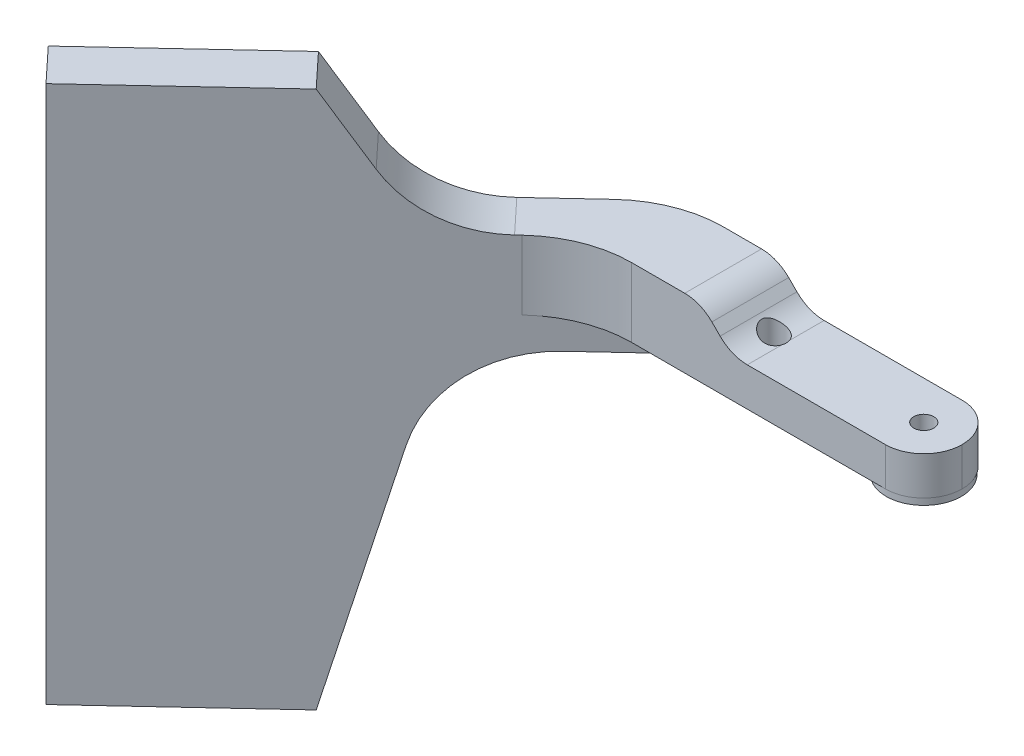
SolidWorks part; units mm, degrees
ref_plane "Front" through (0, 0, 0) normal (0, 0, 1) x (1, 0, 0)
ref_plane "Top" through (0, 0, 0) normal (0, 1, 0) x (1, 0, 0)
ref_plane "Right" through (0, 0, 0) normal (1, 0, 0) x (0, 0, -1)
sketch "Sketch1" plane through (0, 0, 0) normal (0, 1, 0) x (1, 0, 0)
  line L0 (0, 10) -> (0, 0)
  line L1 (0, 0) -> (42, 0)
  line L3 (0, 10) -> (42, 10)
  line L4 (42, 0) -> (42, 10)
  line L9 (0, 10) -> (-42.4185, -29.5559)
  line L10 (-42.4185, -29.5559) -> (-38.3265, -33.944)
  line L11 (0, 10) -> (4.092, 5.6119)
  line L12 (-38.3265, -33.944) -> (4.092, 5.6119)
  line L13 (0, 0) -> (-1.926, 0)
  line L14 (-1.926, 0) -> (0, 1.796)
  line L15 (0, 1.796) -> (0, 0)
  dimension "D1" = 10
  dimension "D2" = 42
  dimension "D3" = 223
  dimension "D4" = 58
  dimension "D5" = 6
  dimension "D6" = 270
extrude "Boss-Extrude1" add sketch "Sketch1" along normal blind 5 contours L10 L12 L1 L0 L9 | L1 L12 L11 L0 | L12 L1 L4 L3 L11 | L13 L0 L12
fillet "Fillet1" radius 5 2 edges at (42, 2.5, 0) (42, 2.5, -10)
sketch "Sketch2" plane through (0, 5, 0) normal (0, 1, 0) x (1, 0, 0)
  circle A0 centre (37, 5) radius 1.3
extrude "Cut-Extrude1" cut sketch "Sketch2" against normal blind 10
sketch "Sketch3" plane through (0, 5, 0) normal (0, 1, 0) x (1, 0, 0)
  line L0 (-42.4185, -29.5559) -> (-38.3265, -33.944)
  line L1 (-38.3265, -33.944) -> (-20.1263, -16.972)
  line L2 (-38.3265, -33.944) -> (-1.926, 0) construction
  line L3 (-20.1263, -16.972) -> (-24.2183, -12.5839)
  line L4 (0, 10) -> (-42.4185, -29.5559) construction
  line L5 (-24.2183, -12.5839) -> (-42.4185, -29.5559)
extrude "Boss-Extrude2" add sketch "Sketch3" along normal blind 20
sketch "Sketch4" plane through (0, 0, 0) normal (0, -1, 0) x (1, 0, 0)
  line L0 (-42.4185, 29.5559) -> (-38.3265, 33.944)
  line L1 (-38.3265, 33.944) -> (-20.1263, 16.972)
  line L2 (-38.3265, 33.944) -> (-1.926, 0) construction
  line L3 (-20.1263, 16.972) -> (-24.2183, 12.5839)
  line L4 (0, -10) -> (-42.4185, 29.5559) construction
  line L5 (-24.2183, 12.5839) -> (-42.4185, 29.5559)
extrude "Boss-Extrude3" add sketch "Sketch4" along normal blind 45
sketch "Sketch5" plane through (-4.9878, 0, -5.3488) normal (-0.682, 0, -0.7314) x (-0.7314, 0, 0.682)
  line L0 (26.2943, -45) -> (26.2943, 0)
  line L1 (26.2943, 0) -> (13.889, 0)
  line L2 (-6.82, 0) -> (26.2943, 0) construction
  line L3 (13.889, 0) -> (26.2943, -45)
  line L4 (13.889, 5) -> (26.2943, 25)
  line L5 (-6.82, 5) -> (26.2943, 5) construction
  line L6 (26.2943, 25) -> (26.2943, 5)
  line L7 (26.2943, 5) -> (13.889, 5)
extrude "Boss-Extrude4" add sketch "Sketch5" against normal blind 6
sketch "Sketch6" plane through (0, 0, 0) normal (0, -1, 0) x (1, 0, 0)
  circle A0 centre (37, -5) radius 4.9
  circle A1 centre (37, -5) radius 1.3
extrude "Boss-Extrude5" add sketch "Sketch6" along normal blind 0.9
sketch "Sketch8" plane through (0, 0, 0) normal (0, -1, 0) x (1, 0, 0)
  line L0 (0, -10) -> (-19.6819, 8.3537)
  line L1 (-24.2183, 12.5839) -> (-15.1456, 4.1235) construction
  line L6 (-19.6819, 8.3537) -> (-15.5899, 12.7418)
  line L7 (-20.1263, 16.972) -> (-11.0536, 8.5116) construction
  line L8 (-15.5899, 12.7418) -> (8.7977, -10)
  line L9 (0, -10) -> (37, -10) construction
  line L10 (8.7977, -10) -> (0, -10)
extrude "Boss-Extrude6" add sketch "Sketch8" along normal blind 4
sketch "Sketch9" plane through (0, 5, 0) normal (0, 1, 0) x (1, 0, 0)
  line L3 (-15.952, -4.8755) -> (-24.2183, -12.5839) construction
  line L4 (-20.0851, -8.7297) -> (0, 10)
  line L6 (-20.0851, -8.7297) -> (-16.7996, -13.8699)
  line L7 (-20.1263, -16.972) -> (-11.0536, -8.5116) construction
  line L9 (-16.7996, -13.8699) -> (8.7977, 10)
  line L10 (0, 10) -> (37, 10) construction
  line L11 (8.7977, 10) -> (0, 10)
  line L12 (37, 0) -> (-1.926, 0) construction
  line L13 (8.7977, 0) -> (-1.926, 0)
  line L14 (-1.926, 0) -> (8.7977, 10)
  line L15 (8.7977, 10) -> (17.9505, 10)
  line L16 (17.9505, 10) -> (17.9505, 0)
  line L17 (17.9505, 0) -> (8.7977, 0)
extrude "Boss-Extrude7" add sketch "Sketch9" along normal blind 4
fillet "Fillet2" radius 15 4 edges at (-13.906, -4, 7.0696) (-14.9141, 9, 8.0096) (-1.926, 4.5, 0) (0, 2.5, -10)
fillet "Fillet7" radius 5 1 edges at (17.9505, 9, -5) profile chamfer
fillet "Fillet8" radius 5 2 edges at (12.9505, 9, -5) (16.9505, 5, -5)
sketch "Sketch11" plane through (0, 0, 0) normal (0, -1, 0) x (-1, 0, 0)
  circle A0 centre (-17.5, 5) radius 1.6
extrude "Cut-Extrude2" cut sketch "Sketch11" against normal blind 10
